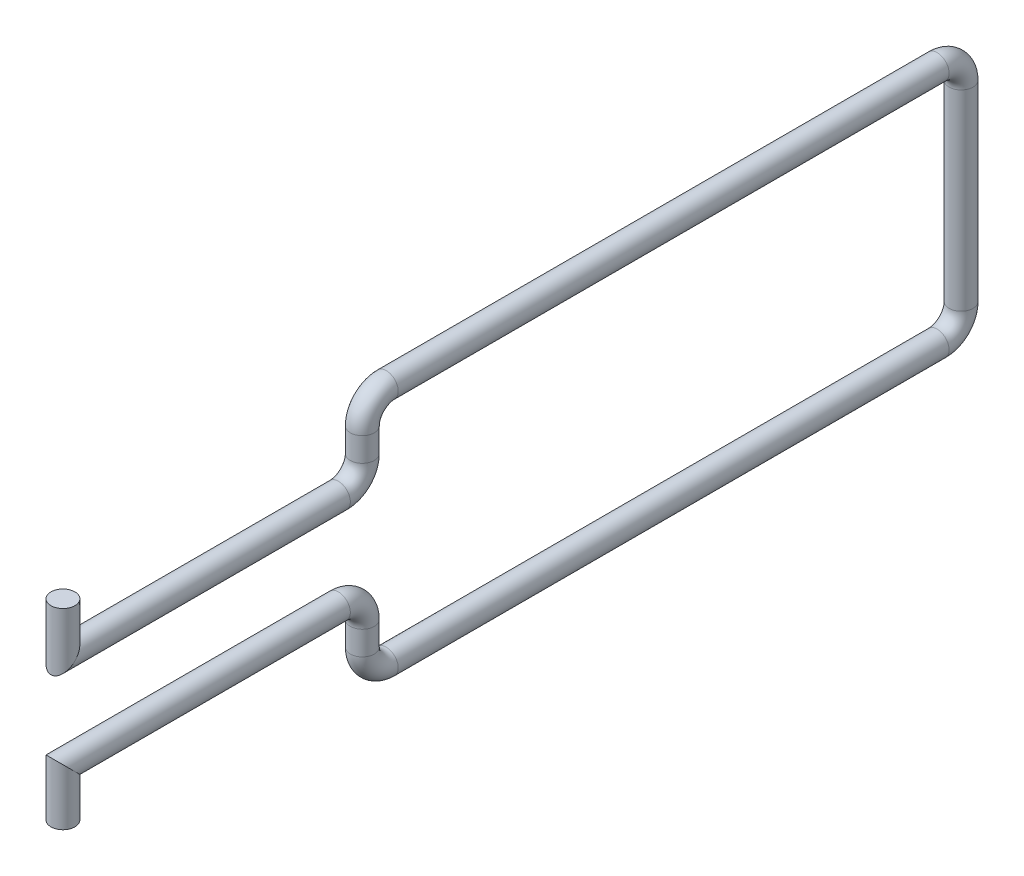
SolidWorks part; units mm, degrees
ref_plane "Vorne" through (0, 0, 0) normal (0, 0, 1) x (1, 0, 0)
ref_plane "Oben" through (0, 0, 0) normal (0, 1, 0) x (1, 0, 0)
ref_plane "Rechts" through (0, 0, 0) normal (1, 0, 0) x (0, 0, -1)
sketch "Skizze1" plane through (0, 0, 0) normal (1, 0, 0) x (0, 0, -1)
  line L0 (0, 4) -> (23, 4)
  line L1 (25, 6) -> (25, 8)
  line L2 (27, 10) -> (73, 10)
  line L3 (75, 8) -> (75, -8)
  line L4 (73, -10) -> (27, -10)
  line L5 (25, -8) -> (25, -6)
  line L6 (23, -4) -> (0, -4)
  line L7 (0, 4) -> (0, 8)
  line L8 (0, -4) -> (0, -8)
  arc A0 (27, -10) -> (25, -8) centre (27, -8) cw
  arc A1 (25, -6) -> (23, -4) centre (23, -6) ccw
  arc A2 (23, 4) -> (25, 6) centre (23, 6) ccw
  arc A3 (25, 8) -> (27, 10) centre (27, 8) cw
  arc A4 (73, -10) -> (75, -8) centre (73, -8) ccw
  arc A5 (75, 8) -> (73, 10) centre (73, 8) ccw
  point P11 (25, -10)
  point P14 (25, -4)
  point P17 (25, 4)
  point P20 (25, 10)
  point P23 (75, -10)
  point P26 (75, 10)
  dimension "D10" = 2
  dimension "D1" = 4
  dimension "D2" = 25
  dimension "D3" = 50
  dimension "D4" = 20
  dimension "D5" = 6
  dimension "D6" = 6
  dimension "D7" = 25
  dimension "D8" = 50
  dimension "D9" = 0
  dimension "D11" = 4
  dimension "D12" = 4
ref_axis "Achse1" through (0, 0, -80.9) along (0, 0, 1)
ref_plane "Ebene1" through (0, 8, 0) normal (0, 1, 0) x (1, 0, 0)
sketch "Skizze5" plane through (0, 8, 0) normal (0, 1, 0) x (1, 0, 0)
  circle A0 centre (0, 0) radius 1
  dimension "D1" = 2
sweep "Austragung1" add profiles "Skizze5" path "Skizze1"
